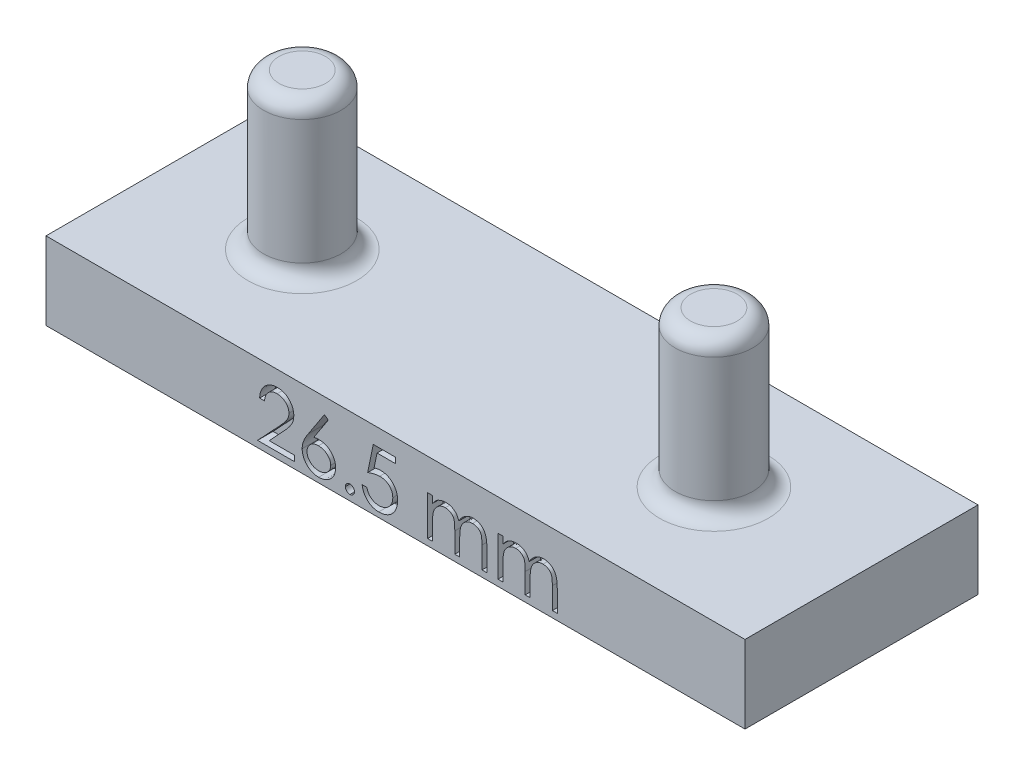
SolidWorks part; units mm, degrees
ref_plane "Front Plane" through (0, 0, 0) normal (0, 0, 1) x (1, 0, 0)
ref_plane "Top Plane" through (0, 0, 0) normal (0, 1, 0) x (1, 0, 0)
ref_plane "Right Plane" through (0, 0, 0) normal (1, 0, 0) x (0, 0, -1)
sketch "Sketch1" plane through (0, 0, 0) normal (0, 1, 0) x (1, 0, 0)
  circle A0 centre (-41.8213, 3.1021) radius 2.5
  circle A1 centre (-15.3213, 3.1021) radius 2.5
  dimension "D1" = 26.5
extrude "Boss-Extrude1" add sketch "Sketch1" along normal blind 10
sketch "Sketch2" plane through (0, 0, 0) normal (0, -1, 0) x (1, 0, 0)
  line L1 (-50.8213, 4.3979) -> (-5.8213, 4.3979)
  line L2 (-50.8213, 4.3979) -> (-50.8213, -10.6021)
  line L3 (-50.8213, -10.6021) -> (-5.8213, -10.6021)
  line L4 (-5.8213, 4.3979) -> (-5.8213, -10.6021)
  circle A0 centre (-41.8213, -3.1021) radius 2.5 construction
  dimension "D1" = 45
  dimension "D2" = 15
  dimension "D3" = 7.5
  dimension "D4" = 9
extrude "Boss-Extrude2" add sketch "Sketch2" along normal blind 5
sketch "Sketch3" plane through (0, 0, 4.3979) normal (0, 0, 1) x (1, 0, 0)
  line L0 (-7.1347, -4.5918) -> (-47.7505, -4.5918) construction
  text T0 "26.5 mm"
extrude "Cut-Extrude1" cut sketch "Sketch3" against normal blind 1
fillet "Fillet1" radius 1 4 edges at (-41.8213, 0, -0.6021) (-15.3213, 0, -5.6021) (-15.3213, 10, -0.6021) (-41.8213, 10, -0.6021)
